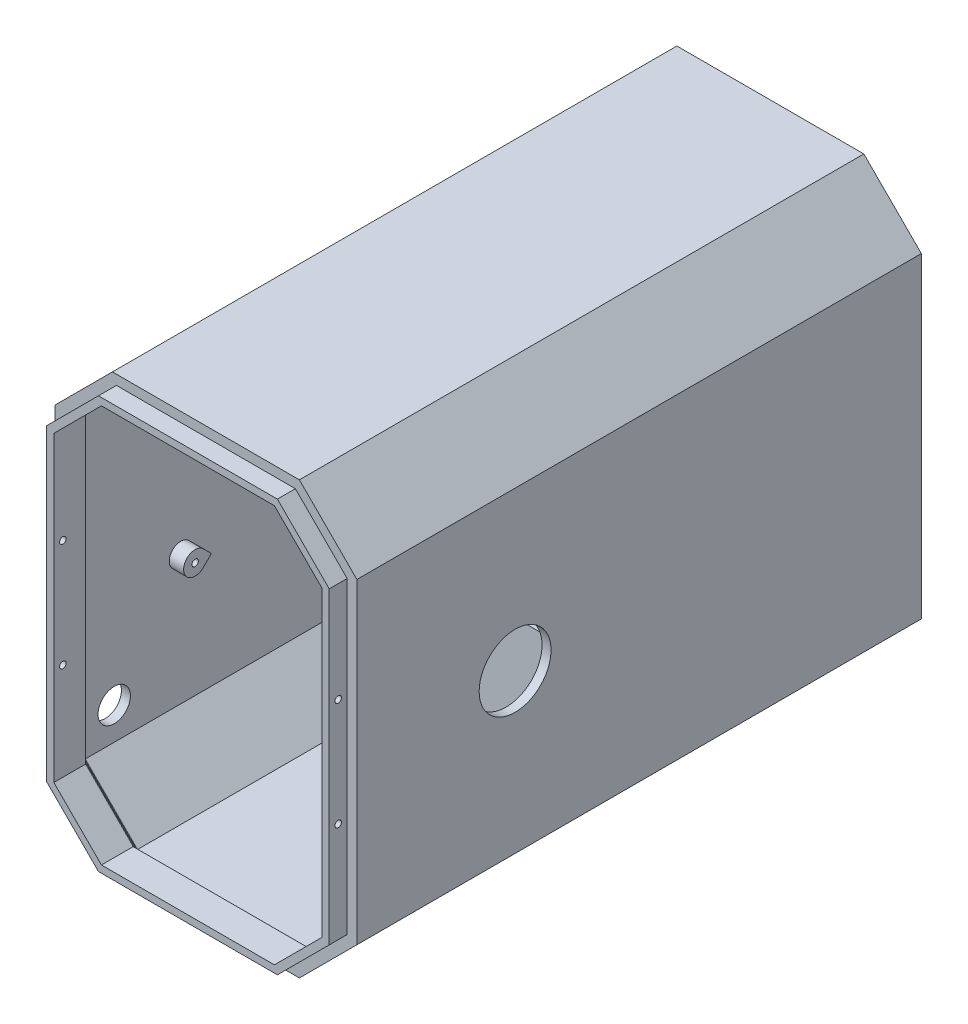
SolidWorks part; units mm, degrees
ref_plane "Front Plane" through (0, 0, 0) normal (0, 0, 1) x (1, 0, 0)
ref_plane "Top Plane" through (0, 0, 0) normal (0, 1, 0) x (1, 0, 0)
ref_plane "Right Plane" through (0, 0, 0) normal (1, 0, 0) x (0, 0, -1)
ref_plane "PZ_p37_000" through (0, 0, 37) normal (0, 0, 1) x (1, 0, 0)
sketch "S_prism1" plane through (0, 0, 37) normal (0, 0, 1) x (1, 0, 0)
  line L0 (42, -44) -> (42, 44)
  line L1 (42, 44) -> (26, 60)
  line L2 (26, 60) -> (-26, 60)
  line L3 (-26, 60) -> (-42, 44)
  line L4 (-42, 44) -> (-42, -44)
  line L5 (-42, -44) -> (-26, -60)
  line L6 (-26, -60) -> (26, -60)
  line L7 (26, -60) -> (42, -44)
extrude "Boss_1" add sketch "S_prism1" along normal blind 157
ref_plane "PZ_p71_425" through (0, 0, 71.425) normal (0, 0, 1) x (1, 0, 0)
sketch "S_pcut2" plane through (0, 0, 71.425) normal (0, 0, 1) x (1, 0, 0)
  line L0 (39.5, -42.9645) -> (39.5, 42.9645)
  line L1 (39.5, 42.9645) -> (24.9645, 57.5)
  line L2 (24.9645, 57.5) -> (-24.9645, 57.5)
  line L3 (-24.9645, 57.5) -> (-39.5, 42.9645)
  line L4 (-39.5, 42.9645) -> (-39.5, -42.9645)
  line L5 (-39.5, -42.9645) -> (-24.9645, -57.5)
  line L6 (-24.9645, -57.5) -> (24.9645, -57.5)
  line L7 (24.9645, -57.5) -> (39.5, -42.9645)
extrude "Cut_2" cut sketch "S_pcut2" along normal blind 122.675
ref_plane "PZ_p36_900" through (0, 0, 36.9) normal (0, 0, 1) x (1, 0, 0)
sketch "S_pcut3" plane through (0, 0, 36.9) normal (0, 0, 1) x (1, 0, 0)
  line L0 (39.5, -42.9645) -> (39.5, 42.9645)
  line L1 (39.5, 42.9645) -> (24.9645, 57.5)
  line L2 (24.9645, 57.5) -> (-24.9645, 57.5)
  line L3 (-24.9645, 57.5) -> (-39.5, 42.9645)
  line L4 (-39.5, 42.9645) -> (-39.5, -42.9645)
  line L5 (-39.5, -42.9645) -> (-24.9645, -57.5)
  line L6 (-24.9645, -57.5) -> (24.9645, -57.5)
  line L7 (24.9645, -57.5) -> (39.5, -42.9645)
extrude "Cut_3" cut sketch "S_pcut3" along normal blind 32.025
ref_plane "PZ_p68_825" through (0, 0, 68.825) normal (0, 0, 1) x (1, 0, 0)
sketch "S_cut4" plane through (0, 0, 68.825) normal (0, 0, 1) x (1, 0, 0)
  line L0 (-34, -14) -> (-26, -14)
  line L1 (-26, -14) -> (-26, 14)
  line L2 (-26, 14) -> (-34, 14)
  line L3 (-34, 14) -> (-34, -14)
  dimension "P1" = 34
  dimension "P2" = 14
  dimension "P3" = 26
  dimension "P4" = 14
  dimension "P5" = 26
  dimension "P6" = 14
  dimension "P7" = 34
  dimension "P8" = 14
extrude "Pocket_4" cut sketch "S_cut4" along normal blind 2.7
ref_plane "PX_m42_100" through (-42.1, 0, 0) normal (1, 0, 0) x (0, 0, -1)
sketch "S_hole5" plane through (-42.1, 0, 0) normal (1, 0, 0) x (0, 0, -1)
  circle A0 centre (-88, 0) radius 6
  dimension "D1_S_hole5" = 12
  dimension "P2" = 88
extrude "Hole_5" cut sketch "S_hole5" along normal blind 2.7
sketch "S_hole6" plane through (-42.1, 0, 0) normal (1, 0, 0) x (0, 0, -1)
  circle A0 centre (-180, -34) radius 4.5
  dimension "D1_S_hole6" = 9
  dimension "P2" = 180
  dimension "P3" = 34
extrude "Hole_6" cut sketch "S_hole6" along normal blind 2.7
sketch "S_cut7" plane through (0, 0, 68.825) normal (0, 0, 1) x (1, 0, 0)
  line L0 (-9.7, 27.8) -> (9.7, 27.8)
  line L1 (9.7, 27.8) -> (9.7, 34.1)
  line L2 (9.7, 34.1) -> (-9.7, 34.1)
  line L3 (-9.7, 34.1) -> (-9.7, 27.8)
  dimension "P1" = 9.7
  dimension "P2" = 27.8
  dimension "P3" = 9.7
  dimension "P4" = 27.8
  dimension "P5" = 9.7
  dimension "P6" = 34.1
  dimension "P7" = 9.7
  dimension "P8" = 34.1
extrude "Pocket_7" cut sketch "S_cut7" along normal blind 2.7
sketch "S_cut8" plane through (0, 0, 68.825) normal (0, 0, 1) x (1, 0, 0)
  line L0 (-9.7, -34.1) -> (9.7, -34.1)
  line L1 (9.7, -34.1) -> (9.7, -27.8)
  line L2 (9.7, -27.8) -> (-9.7, -27.8)
  line L3 (-9.7, -27.8) -> (-9.7, -34.1)
  dimension "P1" = 9.7
  dimension "P2" = 34.1
  dimension "P3" = 9.7
  dimension "P4" = 34.1
  dimension "P5" = 9.7
  dimension "P6" = 27.8
  dimension "P7" = 9.7
  dimension "P8" = 27.8
extrude "Pocket_8" cut sketch "S_cut8" along normal blind 2.7
sketch "S_hole9" plane through (0, 0, 68.825) normal (0, 0, 1) x (1, 0, 0)
  circle A0 centre (-20, -25) radius 1.7
  dimension "D1_S_hole9" = 3.4
  dimension "P2" = 20
  dimension "P3" = 25
extrude "Hole_9" cut sketch "S_hole9" along normal blind 2.7
sketch "S_hole10" plane through (0, 0, 68.825) normal (0, 0, 1) x (1, 0, 0)
  circle A0 centre (-20, 25) radius 1.7
  dimension "D1_S_hole10" = 3.4
  dimension "P2" = 20
  dimension "P3" = 25
extrude "Hole_10" cut sketch "S_hole10" along normal blind 2.7
sketch "S_hole11" plane through (0, 0, 68.825) normal (0, 0, 1) x (1, 0, 0)
  circle A0 centre (24, -25) radius 1.7
  dimension "D1_S_hole11" = 3.4
  dimension "P2" = 24
  dimension "P3" = 25
extrude "Hole_11" cut sketch "S_hole11" along normal blind 2.7
sketch "S_hole12" plane through (0, 0, 68.825) normal (0, 0, 1) x (1, 0, 0)
  circle A0 centre (24, 25) radius 1.7
  dimension "D1_S_hole12" = 3.4
  dimension "P2" = 24
  dimension "P3" = 25
extrude "Hole_12" cut sketch "S_hole12" along normal blind 2.7
ref_plane "PZ_p104_200" through (0, 0, 104.2) normal (0, 0, 1) x (1, 0, 0)
sketch "S_cut13" plane through (0, 0, 104.2) normal (0, 0, 1) x (1, 0, 0)
  line L0 (-37.3, 39.5) -> (-27.3, 39.5)
  line L1 (-27.3, 39.5) -> (-27.3, 61)
  line L2 (-27.3, 61) -> (-37.3, 61)
  line L3 (-37.3, 61) -> (-37.3, 39.5)
  dimension "P1" = 37.3
  dimension "P2" = 39.5
  dimension "P3" = 27.3
  dimension "P4" = 39.5
  dimension "P5" = 27.3
  dimension "P6" = 61
  dimension "P7" = 37.3
  dimension "P8" = 61
extrude "Pocket_13" cut sketch "S_cut13" along normal blind 56.3
ref_plane "PZ_p188_000" through (0, 0, 188) normal (0, 0, 1) x (1, 0, 0)
sketch "S_prism14" plane through (0, 0, 188) normal (0, 0, 1) x (1, 0, 0)
  line L0 (40, -43.1716) -> (40, 43.1716)
  line L1 (40, 43.1716) -> (25.1716, 58)
  line L2 (25.1716, 58) -> (-25.1716, 58)
  line L3 (-25.1716, 58) -> (-40, 43.1716)
  line L4 (-40, 43.1716) -> (-40, -43.1716)
  line L5 (-40, -43.1716) -> (-25.1716, -58)
  line L6 (-25.1716, -58) -> (25.1716, -58)
  line L7 (25.1716, -58) -> (40, -43.1716)
extrude "Boss_14" add sketch "S_prism14" along normal blind 6
ref_plane "PZ_p193_900" through (0, 0, 193.9) normal (0, 0, 1) x (1, 0, 0)
sketch "S_prism15" plane through (0, 0, 193.9) normal (0, 0, 1) x (1, 0, 0)
  line L0 (39.3, -42.8816) -> (39.3, 42.8816)
  line L1 (39.3, 42.8816) -> (24.8816, 57.3)
  line L2 (24.8816, 57.3) -> (-24.8816, 57.3)
  line L3 (-24.8816, 57.3) -> (-39.3, 42.8816)
  line L4 (-39.3, 42.8816) -> (-39.3, -42.8816)
  line L5 (-39.3, -42.8816) -> (-24.8816, -57.3)
  line L6 (-24.8816, -57.3) -> (24.8816, -57.3)
  line L7 (24.8816, -57.3) -> (39.3, -42.8816)
extrude "Boss_15" add sketch "S_prism15" along normal blind 5.1
ref_plane "PX_m40_000" through (-40, 0, 0) normal (1, 0, 0) x (0, 0, -1)
sketch "S_cyl16" plane through (-40, 0, 0) normal (1, 0, 0) x (0, 0, -1)
  circle A0 centre (-103.5, 42) radius 3.2
  dimension "D1_S_cyl16" = 6.4
  dimension "P2" = 103.5
  dimension "P3" = 42
extrude "Boss_16" add sketch "S_cyl16" along normal blind 4.5
sketch "S_prism17" plane through (-40, 0, 0) normal (1, 0, 0) x (0, 0, -1)
  line L0 (-101.24, 39.74) -> (-101.24, 44.26)
  line L1 (-101.24, 44.26) -> (-98.97, 42)
  line L2 (-98.97, 42) -> (-101.24, 39.74)
extrude "Boss_17" add sketch "S_prism17" along normal blind 4.5
sketch "S_cyl18" plane through (-40, 0, 0) normal (1, 0, 0) x (0, 0, -1)
  circle A0 centre (-161.5, 42) radius 3.2
  dimension "D1_S_cyl18" = 6.4
  dimension "P2" = 161.5
  dimension "P3" = 42
extrude "Boss_18" add sketch "S_cyl18" along normal blind 4.5
sketch "S_prism19" plane through (-40, 0, 0) normal (1, 0, 0) x (0, 0, -1)
  line L0 (-159.24, 39.74) -> (-159.24, 44.26)
  line L1 (-159.24, 44.26) -> (-156.97, 42)
  line L2 (-156.97, 42) -> (-159.24, 39.74)
extrude "Boss_19" add sketch "S_prism19" along normal blind 4.5
sketch "S_cyl20" plane through (-40, 0, 0) normal (1, 0, 0) x (0, 0, -1)
  circle A0 centre (-103.5, -7) radius 3.2
  dimension "D1_S_cyl20" = 6.4
  dimension "P2" = 103.5
  dimension "P3" = 7
extrude "Boss_20" add sketch "S_cyl20" along normal blind 4.5
sketch "S_prism21" plane through (-40, 0, 0) normal (1, 0, 0) x (0, 0, -1)
  line L0 (-101.24, -9.26) -> (-101.24, -4.74)
  line L1 (-101.24, -4.74) -> (-98.97, -7)
  line L2 (-98.97, -7) -> (-101.24, -9.26)
extrude "Boss_21" add sketch "S_prism21" along normal blind 4.5
sketch "S_cyl22" plane through (-40, 0, 0) normal (1, 0, 0) x (0, 0, -1)
  circle A0 centre (-161.5, -7) radius 3.2
  dimension "D1_S_cyl22" = 6.4
  dimension "P2" = 161.5
  dimension "P3" = 7
extrude "Boss_22" add sketch "S_cyl22" along normal blind 4.5
sketch "S_prism23" plane through (-40, 0, 0) normal (1, 0, 0) x (0, 0, -1)
  line L0 (-159.24, -9.26) -> (-159.24, -4.74)
  line L1 (-159.24, -4.74) -> (-156.97, -7)
  line L2 (-156.97, -7) -> (-159.24, -9.26)
extrude "Boss_23" add sketch "S_prism23" along normal blind 4.5
ref_plane "PZ_p126_200" through (0, 0, 126.2) normal (0, 0, 1) x (1, 0, 0)
sketch "S_box24" plane through (0, 0, 126.2) normal (0, 0, 1) x (1, 0, 0)
  line L0 (14.2, -34.5) -> (40, -34.5)
  line L1 (40, -34.5) -> (40, 34.5)
  line L2 (40, 34.5) -> (14.2, 34.5)
  line L3 (14.2, 34.5) -> (14.2, -34.5)
  dimension "P1" = 14.2
  dimension "P2" = 34.5
  dimension "P3" = 40
  dimension "P4" = 34.5
  dimension "P5" = 40
  dimension "P6" = 34.5
  dimension "P7" = 14.2
  dimension "P8" = 34.5
extrude "Boss_24" add sketch "S_box24" along normal blind 6
ref_plane "PY_m34_500" through (0, -34.5, 0) normal (0, 1, 0) x (1, 0, 0)
sketch "S_prism25" plane through (0, -34.5, 0) normal (0, 1, 0) x (1, 0, 0)
  line L0 (14.2, -126.25) -> (40, -126.25)
  line L1 (40, -126.25) -> (40, -100.4)
  line L2 (40, -100.4) -> (14.2, -126.25)
extrude "Boss_25" add sketch "S_prism25" along normal blind 69
ref_plane "PZ_p71_375" through (0, 0, 71.375) normal (0, 0, 1) x (1, 0, 0)
sketch "S_box26" plane through (0, 0, 71.375) normal (0, 0, 1) x (1, 0, 0)
  line L0 (-19.5, -20.5) -> (11.5, -20.5)
  line L1 (11.5, -20.5) -> (11.5, 20.5)
  line L2 (11.5, 20.5) -> (-19.5, 20.5)
  line L3 (-19.5, 20.5) -> (-19.5, -20.5)
  dimension "P1" = 19.5
  dimension "P2" = 20.5
  dimension "P3" = 11.5
  dimension "P4" = 20.5
  dimension "P5" = 11.5
  dimension "P6" = 20.5
  dimension "P7" = 19.5
  dimension "P8" = 20.5
extrude "Boss_26" add sketch "S_box26" along normal blind 15.05
ref_plane "PZ_p190_200" through (0, 0, 190.2) normal (0, 0, 1) x (1, 0, 0)
sketch "S_pcut27" plane through (0, 0, 190.2) normal (0, 0, 1) x (1, 0, 0)
  line L0 (37.3, -42.0532) -> (37.3, 42.0532)
  line L1 (37.3, 42.0532) -> (24.0532, 55.3)
  line L2 (24.0532, 55.3) -> (-24.0532, 55.3)
  line L3 (-24.0532, 55.3) -> (-37.3, 42.0532)
  line L4 (-37.3, 42.0532) -> (-37.3, -42.0532)
  line L5 (-37.3, -42.0532) -> (-24.0532, -55.3)
  line L6 (-24.0532, -55.3) -> (24.0532, -55.3)
  line L7 (24.0532, -55.3) -> (37.3, -42.0532)
extrude "Cut_27" cut sketch "S_pcut27" along normal blind 8.9
ref_plane "PZ_p187_900" through (0, 0, 187.9) normal (0, 0, 1) x (1, 0, 0)
sketch "S_pcut28" plane through (0, 0, 187.9) normal (0, 0, 1) x (1, 0, 0)
  line L0 (39.48, -42.9562) -> (39.48, 42.9562)
  line L1 (39.48, 42.9562) -> (24.9562, 57.48)
  line L2 (24.9562, 57.48) -> (-24.9562, 57.48)
  line L3 (-24.9562, 57.48) -> (-39.48, 42.9562)
  line L4 (-39.48, 42.9562) -> (-39.48, -42.9562)
  line L5 (-39.48, -42.9562) -> (-24.9562, -57.48)
  line L6 (-24.9562, -57.48) -> (24.9562, -57.48)
  line L7 (24.9562, -57.48) -> (39.48, -42.9562)
extrude "Cut_28" cut sketch "S_pcut28" along normal blind 0.3
ref_plane "PZ_p188_100" through (0, 0, 188.1) normal (0, 0, 1) x (1, 0, 0)
sketch "S_pcut29" plane through (0, 0, 188.1) normal (0, 0, 1) x (1, 0, 0)
  line L0 (39.28, -42.8733) -> (39.28, 42.8733)
  line L1 (39.28, 42.8733) -> (24.8733, 57.28)
  line L2 (24.8733, 57.28) -> (-24.8733, 57.28)
  line L3 (-24.8733, 57.28) -> (-39.28, 42.8733)
  line L4 (-39.28, 42.8733) -> (-39.28, -42.8733)
  line L5 (-39.28, -42.8733) -> (-24.8733, -57.28)
  line L6 (-24.8733, -57.28) -> (24.8733, -57.28)
  line L7 (24.8733, -57.28) -> (39.28, -42.8733)
extrude "Cut_29" cut sketch "S_pcut29" along normal blind 0.3
ref_plane "PZ_p188_300" through (0, 0, 188.3) normal (0, 0, 1) x (1, 0, 0)
sketch "S_pcut30" plane through (0, 0, 188.3) normal (0, 0, 1) x (1, 0, 0)
  line L0 (39.08, -42.7905) -> (39.08, 42.7905)
  line L1 (39.08, 42.7905) -> (24.7905, 57.08)
  line L2 (24.7905, 57.08) -> (-24.7905, 57.08)
  line L3 (-24.7905, 57.08) -> (-39.08, 42.7905)
  line L4 (-39.08, 42.7905) -> (-39.08, -42.7905)
  line L5 (-39.08, -42.7905) -> (-24.7905, -57.08)
  line L6 (-24.7905, -57.08) -> (24.7905, -57.08)
  line L7 (24.7905, -57.08) -> (39.08, -42.7905)
extrude "Cut_30" cut sketch "S_pcut30" along normal blind 0.3
ref_plane "PZ_p188_500" through (0, 0, 188.5) normal (0, 0, 1) x (1, 0, 0)
sketch "S_pcut31" plane through (0, 0, 188.5) normal (0, 0, 1) x (1, 0, 0)
  line L0 (38.88, -42.7077) -> (38.88, 42.7077)
  line L1 (38.88, 42.7077) -> (24.7077, 56.88)
  line L2 (24.7077, 56.88) -> (-24.7077, 56.88)
  line L3 (-24.7077, 56.88) -> (-38.88, 42.7077)
  line L4 (-38.88, 42.7077) -> (-38.88, -42.7077)
  line L5 (-38.88, -42.7077) -> (-24.7077, -56.88)
  line L6 (-24.7077, -56.88) -> (24.7077, -56.88)
  line L7 (24.7077, -56.88) -> (38.88, -42.7077)
extrude "Cut_31" cut sketch "S_pcut31" along normal blind 0.3
ref_plane "PZ_p188_700" through (0, 0, 188.7) normal (0, 0, 1) x (1, 0, 0)
sketch "S_pcut32" plane through (0, 0, 188.7) normal (0, 0, 1) x (1, 0, 0)
  line L0 (38.68, -42.6248) -> (38.68, 42.6248)
  line L1 (38.68, 42.6248) -> (24.6248, 56.68)
  line L2 (24.6248, 56.68) -> (-24.6248, 56.68)
  line L3 (-24.6248, 56.68) -> (-38.68, 42.6248)
  line L4 (-38.68, 42.6248) -> (-38.68, -42.6248)
  line L5 (-38.68, -42.6248) -> (-24.6248, -56.68)
  line L6 (-24.6248, -56.68) -> (24.6248, -56.68)
  line L7 (24.6248, -56.68) -> (38.68, -42.6248)
extrude "Cut_32" cut sketch "S_pcut32" along normal blind 0.3
ref_plane "PZ_p188_900" through (0, 0, 188.9) normal (0, 0, 1) x (1, 0, 0)
sketch "S_pcut33" plane through (0, 0, 188.9) normal (0, 0, 1) x (1, 0, 0)
  line L0 (38.48, -42.542) -> (38.48, 42.542)
  line L1 (38.48, 42.542) -> (24.542, 56.48)
  line L2 (24.542, 56.48) -> (-24.542, 56.48)
  line L3 (-24.542, 56.48) -> (-38.48, 42.542)
  line L4 (-38.48, 42.542) -> (-38.48, -42.542)
  line L5 (-38.48, -42.542) -> (-24.542, -56.48)
  line L6 (-24.542, -56.48) -> (24.542, -56.48)
  line L7 (24.542, -56.48) -> (38.48, -42.542)
extrude "Cut_33" cut sketch "S_pcut33" along normal blind 0.3
ref_plane "PZ_p189_100" through (0, 0, 189.1) normal (0, 0, 1) x (1, 0, 0)
sketch "S_pcut34" plane through (0, 0, 189.1) normal (0, 0, 1) x (1, 0, 0)
  line L0 (38.28, -42.4591) -> (38.28, 42.4591)
  line L1 (38.28, 42.4591) -> (24.4591, 56.28)
  line L2 (24.4591, 56.28) -> (-24.4591, 56.28)
  line L3 (-24.4591, 56.28) -> (-38.28, 42.4591)
  line L4 (-38.28, 42.4591) -> (-38.28, -42.4591)
  line L5 (-38.28, -42.4591) -> (-24.4591, -56.28)
  line L6 (-24.4591, -56.28) -> (24.4591, -56.28)
  line L7 (24.4591, -56.28) -> (38.28, -42.4591)
extrude "Cut_34" cut sketch "S_pcut34" along normal blind 0.3
ref_plane "PZ_p189_300" through (0, 0, 189.3) normal (0, 0, 1) x (1, 0, 0)
sketch "S_pcut35" plane through (0, 0, 189.3) normal (0, 0, 1) x (1, 0, 0)
  line L0 (38.08, -42.3763) -> (38.08, 42.3763)
  line L1 (38.08, 42.3763) -> (24.3763, 56.08)
  line L2 (24.3763, 56.08) -> (-24.3763, 56.08)
  line L3 (-24.3763, 56.08) -> (-38.08, 42.3763)
  line L4 (-38.08, 42.3763) -> (-38.08, -42.3763)
  line L5 (-38.08, -42.3763) -> (-24.3763, -56.08)
  line L6 (-24.3763, -56.08) -> (24.3763, -56.08)
  line L7 (24.3763, -56.08) -> (38.08, -42.3763)
extrude "Cut_35" cut sketch "S_pcut35" along normal blind 0.3
ref_plane "PZ_p189_500" through (0, 0, 189.5) normal (0, 0, 1) x (1, 0, 0)
sketch "S_pcut36" plane through (0, 0, 189.5) normal (0, 0, 1) x (1, 0, 0)
  line L0 (37.88, -42.2934) -> (37.88, 42.2934)
  line L1 (37.88, 42.2934) -> (24.2934, 55.88)
  line L2 (24.2934, 55.88) -> (-24.2934, 55.88)
  line L3 (-24.2934, 55.88) -> (-37.88, 42.2934)
  line L4 (-37.88, 42.2934) -> (-37.88, -42.2934)
  line L5 (-37.88, -42.2934) -> (-24.2934, -55.88)
  line L6 (-24.2934, -55.88) -> (24.2934, -55.88)
  line L7 (24.2934, -55.88) -> (37.88, -42.2934)
extrude "Cut_36" cut sketch "S_pcut36" along normal blind 0.3
ref_plane "PZ_p189_700" through (0, 0, 189.7) normal (0, 0, 1) x (1, 0, 0)
sketch "S_pcut37" plane through (0, 0, 189.7) normal (0, 0, 1) x (1, 0, 0)
  line L0 (37.68, -42.2106) -> (37.68, 42.2106)
  line L1 (37.68, 42.2106) -> (24.2106, 55.68)
  line L2 (24.2106, 55.68) -> (-24.2106, 55.68)
  line L3 (-24.2106, 55.68) -> (-37.68, 42.2106)
  line L4 (-37.68, 42.2106) -> (-37.68, -42.2106)
  line L5 (-37.68, -42.2106) -> (-24.2106, -55.68)
  line L6 (-24.2106, -55.68) -> (24.2106, -55.68)
  line L7 (24.2106, -55.68) -> (37.68, -42.2106)
extrude "Cut_37" cut sketch "S_pcut37" along normal blind 0.3
ref_plane "PZ_p189_900" through (0, 0, 189.9) normal (0, 0, 1) x (1, 0, 0)
sketch "S_pcut38" plane through (0, 0, 189.9) normal (0, 0, 1) x (1, 0, 0)
  line L0 (37.48, -42.1278) -> (37.48, 42.1278)
  line L1 (37.48, 42.1278) -> (24.1278, 55.48)
  line L2 (24.1278, 55.48) -> (-24.1278, 55.48)
  line L3 (-24.1278, 55.48) -> (-37.48, 42.1278)
  line L4 (-37.48, 42.1278) -> (-37.48, -42.1278)
  line L5 (-37.48, -42.1278) -> (-24.1278, -55.48)
  line L6 (-24.1278, -55.48) -> (24.1278, -55.48)
  line L7 (24.1278, -55.48) -> (37.48, -42.1278)
extrude "Cut_38" cut sketch "S_pcut38" along normal blind 0.3
ref_plane "PX_p37_100" through (37.1, 0, 0) normal (1, 0, 0) x (0, 0, -1)
sketch "S_hole39" plane through (37.1, 0, 0) normal (1, 0, 0) x (0, 0, -1)
  circle A0 centre (-196.5, -15) radius 0.9
  dimension "D1_S_hole39" = 1.8
  dimension "P2" = 196.5
  dimension "P3" = 15
extrude "Hole_39" cut sketch "S_hole39" along normal blind 2.7
sketch "S_hole40" plane through (37.1, 0, 0) normal (1, 0, 0) x (0, 0, -1)
  circle A0 centre (-196.5, 15) radius 0.9
  dimension "D1_S_hole40" = 1.8
  dimension "P2" = 196.5
  dimension "P3" = 15
extrude "Hole_40" cut sketch "S_hole40" along normal blind 2.7
ref_plane "PX_m39_800" through (-39.8, 0, 0) normal (1, 0, 0) x (0, 0, -1)
sketch "S_hole41" plane through (-39.8, 0, 0) normal (1, 0, 0) x (0, 0, -1)
  circle A0 centre (-196.5, -15) radius 0.9
  dimension "D1_S_hole41" = 1.8
  dimension "P2" = 196.5
  dimension "P3" = 15
extrude "Hole_41" cut sketch "S_hole41" along normal blind 2.7
sketch "S_hole42" plane through (-39.8, 0, 0) normal (1, 0, 0) x (0, 0, -1)
  circle A0 centre (-196.5, 15) radius 0.9
  dimension "D1_S_hole42" = 1.8
  dimension "P2" = 196.5
  dimension "P3" = 15
extrude "Hole_42" cut sketch "S_hole42" along normal blind 2.7
ref_plane "PX_m40_600" through (-40.6, 0, 0) normal (1, 0, 0) x (0, 0, -1)
sketch "S_hole43" plane through (-40.6, 0, 0) normal (1, 0, 0) x (0, 0, -1)
  circle A0 centre (-103.5, 42) radius 0.9
  dimension "D1_S_hole43" = 1.8
  dimension "P2" = 103.5
  dimension "P3" = 42
extrude "Hole_43" cut sketch "S_hole43" along normal blind 5.2
sketch "S_hole44" plane through (-40.6, 0, 0) normal (1, 0, 0) x (0, 0, -1)
  circle A0 centre (-161.5, 42) radius 0.9
  dimension "D1_S_hole44" = 1.8
  dimension "P2" = 161.5
  dimension "P3" = 42
extrude "Hole_44" cut sketch "S_hole44" along normal blind 5.2
sketch "S_hole45" plane through (-40.6, 0, 0) normal (1, 0, 0) x (0, 0, -1)
  circle A0 centre (-103.5, -7) radius 0.9
  dimension "D1_S_hole45" = 1.8
  dimension "P2" = 103.5
  dimension "P3" = 7
extrude "Hole_45" cut sketch "S_hole45" along normal blind 5.2
sketch "S_hole46" plane through (-40.6, 0, 0) normal (1, 0, 0) x (0, 0, -1)
  circle A0 centre (-161.5, -7) radius 0.9
  dimension "D1_S_hole46" = 1.8
  dimension "P2" = 161.5
  dimension "P3" = 7
extrude "Hole_46" cut sketch "S_hole46" along normal blind 5.2
ref_plane "PX_p39_000" through (39, 0, 0) normal (1, 0, 0) x (0, 0, -1)
sketch "S_hole47" plane through (39, 0, 0) normal (1, 0, 0) x (0, 0, -1)
  circle A0 centre (-150, 0) radius 10
  dimension "D1_S_hole47" = 20
  dimension "P2" = 150
extrude "Hole_47" cut sketch "S_hole47" along normal blind 3.1
ref_plane "PZ_p128_200" through (0, 0, 128.2) normal (0, 0, 1) x (1, 0, 0)
sketch "S_cut48" plane through (0, 0, 128.2) normal (0, 0, 1) x (1, 0, 0)
  line L0 (14.1, -5) -> (39, -5)
  line L1 (39, -5) -> (39, 5)
  line L2 (39, 5) -> (14.1, 5)
  line L3 (14.1, 5) -> (14.1, -5)
  dimension "P1" = 14.1
  dimension "P2" = 5
  dimension "P3" = 39
  dimension "P4" = 5
  dimension "P5" = 39
  dimension "P6" = 5
  dimension "P7" = 14.1
  dimension "P8" = 5
extrude "Pocket_48" cut sketch "S_cut48" along normal blind 4.1
ref_plane "PX_p14_100" through (14.1, 0, 0) normal (1, 0, 0) x (0, 0, -1)
sketch "S_hole49" plane through (14.1, 0, 0) normal (1, 0, 0) x (0, 0, -1)
  circle A0 centre (-129.2, -22) radius 0.9
  dimension "D1_S_hole49" = 1.8
  dimension "P2" = 129.2
  dimension "P3" = 22
extrude "Hole_49" cut sketch "S_hole49" along normal blind 9.1
sketch "S_hole50" plane through (14.1, 0, 0) normal (1, 0, 0) x (0, 0, -1)
  circle A0 centre (-129.2, 22) radius 0.9
  dimension "D1_S_hole50" = 1.8
  dimension "P2" = 129.2
  dimension "P3" = 22
extrude "Hole_50" cut sketch "S_hole50" along normal blind 9.1
sketch "S_cut51" plane through (0, 0, 71.425) normal (0, 0, 1) x (1, 0, 0)
  line L0 (-17.5, -18.5) -> (9.5, -18.5)
  line L1 (9.5, -18.5) -> (9.5, 18.5)
  line L2 (9.5, 18.5) -> (-17.5, 18.5)
  line L3 (-17.5, 18.5) -> (-17.5, -18.5)
  dimension "P1" = 17.5
  dimension "P2" = 18.5
  dimension "P3" = 9.5
  dimension "P4" = 18.5
  dimension "P5" = 9.5
  dimension "P6" = 18.5
  dimension "P7" = 17.5
  dimension "P8" = 18.5
extrude "Pocket_51" cut sketch "S_cut51" along normal blind 15.1
ref_plane "PZ_p80_425" through (0, 0, 80.425) normal (0, 0, 1) x (1, 0, 0)
sketch "S_cut52" plane through (0, 0, 80.425) normal (0, 0, 1) x (1, 0, 0)
  line L0 (-6, -20.6) -> (-2, -20.6)
  line L1 (-2, -20.6) -> (-2, 20.6)
  line L2 (-2, 20.6) -> (-6, 20.6)
  line L3 (-6, 20.6) -> (-6, -20.6)
  dimension "P1" = 6
  dimension "P2" = 20.6
  dimension "P3" = 2
  dimension "P4" = 20.6
  dimension "P5" = 2
  dimension "P6" = 20.6
  dimension "P7" = 6
  dimension "P8" = 20.6
extrude "Pocket_52" cut sketch "S_cut52" along normal blind 3
equation "\"plate_t\" = 3"
equation "\"clearance\" = 0.5"
